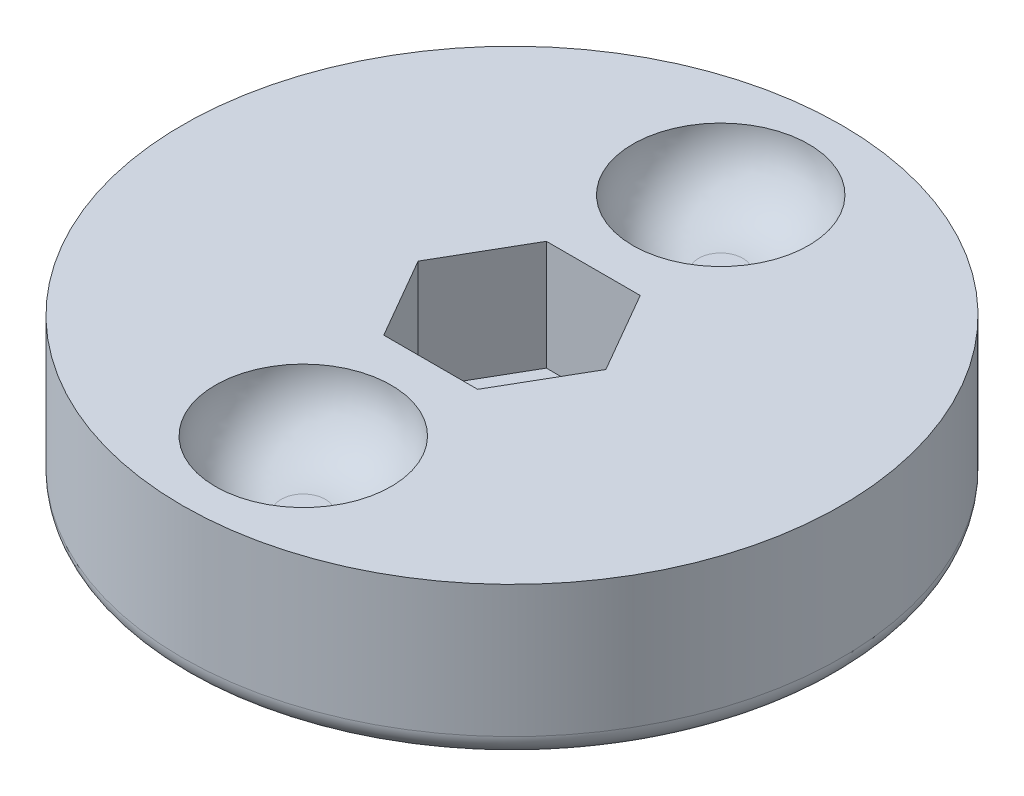
SolidWorks part; units mm, degrees
ref_plane "Front Plane" through (0, 0, 0) normal (0, 0, 1) x (1, 0, 0)
ref_plane "Top Plane" through (0, 0, 0) normal (0, 1, 0) x (1, 0, 0)
ref_plane "Right Plane" through (0, 0, 0) normal (1, 0, 0) x (0, 0, -1)
sketch "Sketch1" plane through (0, 0, 0) normal (0, 1, 0) x (1, 0, 0)
  circle A0 centre (0, 0) radius 19.05
  circle A1 centre (0, 0) radius 2.794
  dimension "D1" = 38.1
  dimension "D2" = 5.588
extrude "Boss-Extrude1" add sketch "Sketch1" along normal blind 2.54
sketch "Sketch2" plane through (0, 2.54, 0) normal (0, 1, 0) x (1, 0, 0)
  line L0 (0, 0) -> (5.4259, 0) construction
  line L1 (5.4259, 0) -> (2.713, 4.699)
  line L2 (2.713, 4.699) -> (-2.713, 4.699)
  line L3 (-2.713, 4.699) -> (-5.4259, 0)
  line L4 (-5.4259, 0) -> (-2.713, -4.699)
  line L5 (-2.713, -4.699) -> (2.713, -4.699)
  line L6 (2.713, -4.699) -> (5.4259, 0)
  circle A0 centre (0, 0) radius 19.05
  circle A1 centre (0, 0) radius 19.05 construction
  circle A2 centre (0, 0) radius 4.699 construction
  dimension "D1" = 9.398
extrude "Boss-Extrude2" add sketch "Sketch2" along normal blind 6.35
sketch "Sketch3" plane through (0, 8.89, 0) normal (0, 1, 0) x (1, 0, 0)
  line L0 (0, 12.065) -> (0, -12.065) construction
  circle A0 centre (0, 12.065) radius 5.08
  circle A1 centre (0, -12.065) radius 5.08
  point P2 (0, 0)
  dimension "D2" = 10.16
  dimension "D1" = 24.13
extrude "Cut-Extrude1" cut sketch "Sketch3" against normal blind 3.81
fillet "Fillet1" radius 3.81 2 edges at (0, 5.08, 17.145) (0, 5.08, -6.985)
fillet "Fillet2" radius 1.27 1 edges at (0, 0, 19.05)
